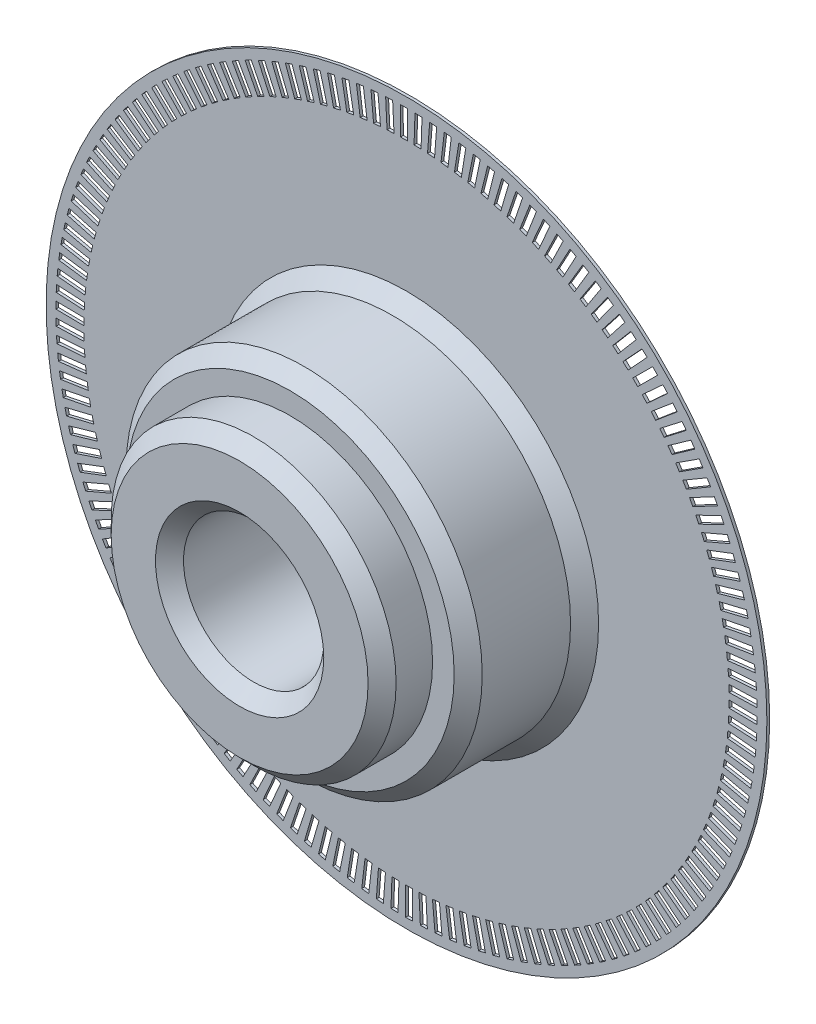
SolidWorks part; units mm, degrees
ref_plane "Płaszczyzna przednia" through (0, 0, 0) normal (0, 0, 1) x (1, 0, 0)
ref_plane "Płaszczyzna górna" through (0, 0, 0) normal (0, 1, 0) x (1, 0, 0)
ref_plane "Płaszczyzna prawa" through (0, 0, 0) normal (1, 0, 0) x (0, 0, -1)
sketch "Szkic1" plane through (0, 0, 0) normal (0, 0, 1) x (1, 0, 0)
  circle A0 centre (0, 0) radius 12.85
  dimension "D1" = 25.7
extrude "Dodanie-wyciągnięcie1" add sketch "Szkic1" along normal blind 0.1 contours A0
sketch "Szkic2" plane through (0, 0, 0.1) normal (0, 0, 1) x (1, 0, 0)
  circle A0 centre (0, 0) radius 6.35
  dimension "D1" = 12.7
extrude "Dodanie-wyciągnięcie2" add sketch "Szkic2" along normal blind 4.15
sketch "Szkic3" plane through (0, 0, 4.25) normal (0, 0, 1) x (1, 0, 0)
  circle A0 centre (0, 0) radius 5.08
  dimension "D1" = 10.16
extrude "Dodanie-wyciągnięcie3" add sketch "Szkic3" along normal blind 1.8
sketch "Szkic5" plane through (0, 0, 0) normal (0, 0, -1) x (-1, 0, 0)
  circle A0 centre (0, 0) radius 2.5
  dimension "D1" = 5
extrude "Wytnij-wyciągnięcie1" cut sketch "Szkic5" against normal through all both and the other way through all
chamfer "Sfazowanie1" distance 0.5 angle 45 5 edges at (5.08, 0, 6.05) (2.5, 0, 0) (-2.5, 0, 6.05) (6.35, 0, 0.1) (6.35, 0, 4.25)
sketch "Szkic7" plane through (0, 0, 0) normal (0, 0, -1) x (-1, 0, 0)
  line L0 (-4.4312, -10.6143) -> (-4.8067, -11.5411)
  line L3 (-3.7474, -10.8746) -> (-4.0838, -11.8163)
  line L4 (-3.7474, -10.8746) -> (-3.9829, -10.7905)
  line L5 (-4.0838, -11.8163) -> (-4.3192, -11.7322)
  line L6 (-3.9829, -10.7905) -> (-4.3192, -11.7322)
  line L7 (-3.7474, -10.8746) -> (-4.3192, -11.7322) construction
  line L8 (-4.0838, -11.8163) -> (-3.9829, -10.7905) construction
  line L9 (-4.1995, -10.7081) -> (-4.575, -11.635)
  line L10 (-4.1995, -10.7081) -> (-4.4312, -10.6143)
  line L11 (-4.575, -11.635) -> (-4.8067, -11.5411)
  line L12 (-4.8718, -10.4194) -> (-5.2858, -11.3297)
  line L13 (-4.6443, -10.5229) -> (-5.0582, -11.4332)
  line L14 (-4.6443, -10.5229) -> (-4.8718, -10.4194)
  line L15 (-5.0582, -11.4332) -> (-5.2858, -11.3297)
  line L16 (-5.3039, -10.2062) -> (-5.7556, -11.0984)
  line L17 (-5.0808, -10.3192) -> (-5.5326, -11.2113)
  line L18 (-5.0808, -10.3192) -> (-5.3039, -10.2062)
  line L19 (-5.5326, -11.2113) -> (-5.7556, -11.0984)
  line L20 (-5.7266, -9.9752) -> (-6.2153, -10.8476)
  line L21 (-5.5085, -10.0973) -> (-5.9972, -10.9698)
  line L22 (-5.5085, -10.0973) -> (-5.7266, -9.9752)
  line L23 (-5.9972, -10.9698) -> (-6.2153, -10.8476)
  line L24 (-6.1393, -9.7266) -> (-6.6641, -10.5779)
  line L25 (-5.9265, -9.8578) -> (-6.4513, -10.709)
  line L26 (-5.9265, -9.8578) -> (-6.1393, -9.7266)
  line L27 (-6.4513, -10.709) -> (-6.6641, -10.5779)
  line L28 (-6.5412, -9.461) -> (-7.1012, -10.2895)
  line L29 (-6.3341, -9.601) -> (-6.8941, -10.4295)
  line L30 (-6.3341, -9.601) -> (-6.5412, -9.461)
  line L31 (-6.8941, -10.4295) -> (-7.1012, -10.2895)
  line L32 (-6.9317, -9.1788) -> (-7.5259, -9.9831)
  line L33 (-6.7306, -9.3273) -> (-7.3248, -10.1317)
  line L34 (-6.7306, -9.3273) -> (-6.9317, -9.1788)
  line L35 (-7.3248, -10.1317) -> (-7.5259, -9.9831)
  line L36 (-7.31, -8.8805) -> (-7.9373, -9.6592)
  line L37 (-7.1153, -9.0373) -> (-7.7426, -9.816)
  line L38 (-7.1153, -9.0373) -> (-7.31, -8.8805)
  line L39 (-7.7426, -9.816) -> (-7.9373, -9.6592)
  line L40 (-7.6754, -8.5666) -> (-8.3348, -9.3184)
  line L41 (-7.4875, -8.7314) -> (-8.1469, -9.4832)
  line L42 (-7.4875, -8.7314) -> (-7.6754, -8.5666)
  line L43 (-8.1469, -9.4832) -> (-8.3348, -9.3184)
  line L44 (-8.0274, -8.2376) -> (-8.7177, -8.9612)
  line L45 (-7.8466, -8.4102) -> (-8.5369, -9.1337)
  line L46 (-7.8466, -8.4102) -> (-8.0274, -8.2376)
  line L47 (-8.5369, -9.1337) -> (-8.7177, -8.9612)
  line L48 (-8.3654, -7.8942) -> (-9.0853, -8.5882)
  line L49 (-8.1919, -8.0742) -> (-8.9118, -8.7682)
  line L50 (-8.1919, -8.0742) -> (-8.3654, -7.8942)
  line L51 (-8.9118, -8.7682) -> (-9.0853, -8.5882)
  line L52 (-8.6886, -7.537) -> (-9.437, -8.2002)
  line L53 (-8.5228, -7.7241) -> (-9.2712, -8.3874)
  line L54 (-8.5228, -7.7241) -> (-8.6886, -7.537)
  line L55 (-9.2712, -8.3874) -> (-9.437, -8.2002)
  line L56 (-8.9966, -7.1666) -> (-9.7721, -7.7979)
  line L57 (-8.8388, -7.3605) -> (-9.6143, -7.9918)
  line L58 (-8.8388, -7.3605) -> (-8.9966, -7.1666)
  line L59 (-9.6143, -7.9918) -> (-9.7721, -7.7979)
  line L60 (-9.2888, -6.7835) -> (-10.0901, -7.3818)
  line L61 (-9.1392, -6.9839) -> (-9.9405, -7.5821)
  line L62 (-9.1392, -6.9839) -> (-9.2888, -6.7835)
  line L63 (-9.9405, -7.5821) -> (-10.0901, -7.3818)
  line L64 (-9.5647, -6.3886) -> (-10.3904, -6.9528)
  line L65 (-9.4237, -6.595) -> (-10.2493, -7.1592)
  line L66 (-9.4237, -6.595) -> (-9.5647, -6.3886)
  line L67 (-10.2493, -7.1592) -> (-10.3904, -6.9528)
  line L68 (-9.8239, -5.9825) -> (-10.6724, -6.5116)
  line L69 (-9.6916, -6.1946) -> (-10.5401, -6.7237)
  line L70 (-9.6916, -6.1946) -> (-9.8239, -5.9825)
  line L71 (-10.5401, -6.7237) -> (-10.6724, -6.5116)
  line L72 (-10.0658, -5.5659) -> (-10.9357, -6.059)
  line L73 (-9.9425, -5.7833) -> (-10.8124, -6.2765)
  line L74 (-9.9425, -5.7833) -> (-10.0658, -5.5659)
  line L75 (-10.8124, -6.2765) -> (-10.9357, -6.059)
  line L76 (-10.29, -5.1395) -> (-11.1798, -5.5957)
  line L77 (-10.1759, -5.3619) -> (-11.0658, -5.8182)
  line L78 (-10.1759, -5.3619) -> (-10.29, -5.1395)
  line L79 (-11.0658, -5.8182) -> (-11.1798, -5.5957)
  line L80 (-10.4962, -4.7041) -> (-11.4044, -5.1227)
  line L81 (-10.3915, -4.9311) -> (-11.2997, -5.3497)
  line L82 (-10.3915, -4.9311) -> (-10.4962, -4.7041)
  line L83 (-11.2997, -5.3497) -> (-11.4044, -5.1227)
  line L84 (-10.684, -4.2604) -> (-11.6089, -4.6406)
  line L85 (-10.5889, -4.4916) -> (-11.5138, -4.8718)
  line L86 (-10.5889, -4.4916) -> (-10.684, -4.2604)
  line L87 (-11.5138, -4.8718) -> (-11.6089, -4.6406)
  line L88 (-10.853, -3.8093) -> (-11.793, -4.1504)
  line L89 (-10.7677, -4.0443) -> (-11.7077, -4.3854)
  line L90 (-10.7677, -4.0443) -> (-10.853, -3.8093)
  line L91 (-11.7077, -4.3854) -> (-11.793, -4.1504)
  line L92 (-11.003, -3.3514) -> (-11.9565, -3.6529)
  line L93 (-10.9276, -3.5898) -> (-11.8811, -3.8913)
  line L94 (-10.9276, -3.5898) -> (-11.003, -3.3514)
  line L95 (-11.8811, -3.8913) -> (-11.9565, -3.6529)
  line L96 (-11.1337, -2.8877) -> (-12.099, -3.149)
  line L97 (-11.0684, -3.1291) -> (-12.0336, -3.3903)
  line L98 (-11.0684, -3.1291) -> (-11.1337, -2.8877)
  line L99 (-12.0336, -3.3903) -> (-12.099, -3.149)
  line L100 (-11.2449, -2.419) -> (-12.2202, -2.6396)
  line L101 (-11.1897, -2.6628) -> (-12.1651, -2.8835)
  line L102 (-11.1897, -2.6628) -> (-11.2449, -2.419)
  line L103 (-12.1651, -2.8835) -> (-12.2202, -2.6396)
  line L104 (-11.3363, -1.946) -> (-12.32, -2.1256)
  line L105 (-11.2914, -2.1919) -> (-12.2751, -2.3715)
  line L106 (-11.2914, -2.1919) -> (-11.3363, -1.946)
  line L107 (-12.2751, -2.3715) -> (-12.32, -2.1256)
  line L108 (-11.4078, -1.4696) -> (-12.3982, -1.6078)
  line L109 (-11.3733, -1.7172) -> (-12.3637, -1.8554)
  line L110 (-11.3733, -1.7172) -> (-11.4078, -1.4696)
  line L111 (-12.3637, -1.8554) -> (-12.3982, -1.6078)
  line L112 (-11.4594, -0.9906) -> (-12.4547, -1.0872)
  line L113 (-11.4352, -1.2394) -> (-12.4305, -1.336)
  line L114 (-11.4352, -1.2394) -> (-11.4594, -0.9906)
  line L115 (-12.4305, -1.336) -> (-12.4547, -1.0872)
  line L116 (-11.4908, -0.5098) -> (-12.4893, -0.5647)
  line L117 (-11.4771, -0.7594) -> (-12.4756, -0.8143)
  line L118 (-11.4771, -0.7594) -> (-11.4908, -0.5098)
  line L119 (-12.4756, -0.8143) -> (-12.4893, -0.5647)
  line L120 (-11.5021, -0.0282) -> (-12.502, -0.0412)
  line L121 (-11.4988, -0.2782) -> (-12.4987, -0.2912)
  line L122 (-11.4988, -0.2782) -> (-11.5021, -0.0282)
  line L123 (-12.4987, -0.2912) -> (-12.502, -0.0412)
  line L124 (-11.4932, 0.4535) -> (-12.4927, 0.4824)
  line L125 (-11.5004, 0.2036) -> (-12.5, 0.2325)
  line L126 (-11.5004, 0.2036) -> (-11.4932, 0.4535)
  line L127 (-12.5, 0.2325) -> (-12.4927, 0.4824)
  line L128 (-11.4641, 0.9344) -> (-12.4616, 1.0051)
  line L129 (-11.4818, 0.685) -> (-12.4793, 0.7557)
  line L130 (-11.4818, 0.685) -> (-11.4641, 0.9344)
  line L131 (-12.4793, 0.7557) -> (-12.4616, 1.0051)
  line L132 (-11.4149, 1.4136) -> (-12.4086, 1.526)
  line L133 (-11.443, 1.1652) -> (-12.4367, 1.2776)
  line L134 (-11.443, 1.1652) -> (-11.4149, 1.4136)
  line L135 (-12.4367, 1.2776) -> (-12.4086, 1.526)
  line L136 (-11.3457, 1.8904) -> (-12.3338, 2.0443)
  line L137 (-11.3842, 1.6434) -> (-12.3723, 1.7973)
  line L138 (-11.3842, 1.6434) -> (-11.3457, 1.8904)
  line L139 (-12.3723, 1.7973) -> (-12.3338, 2.0443)
  line L140 (-11.2566, 2.3638) -> (-12.2374, 2.559)
  line L141 (-11.3054, 2.1187) -> (-12.2861, 2.3138)
  line L142 (-11.3054, 2.1187) -> (-11.2566, 2.3638)
  line L143 (-12.2861, 2.3138) -> (-12.2374, 2.559)
  line L144 (-11.1477, 2.8331) -> (-12.1195, 3.0692)
  line L145 (-11.2067, 2.5902) -> (-12.1785, 2.8263)
  line L146 (-11.2067, 2.5902) -> (-11.1477, 2.8331)
  line L147 (-12.1785, 2.8263) -> (-12.1195, 3.0692)
  line L148 (-11.0193, 3.2975) -> (-11.9803, 3.574)
  line L149 (-11.0884, 3.0572) -> (-12.0494, 3.3338)
  line L150 (-11.0884, 3.0572) -> (-11.0193, 3.2975)
  line L151 (-12.0494, 3.3338) -> (-11.9803, 3.574)
  line L152 (-10.8715, 3.756) -> (-11.8201, 4.0726)
  line L153 (-10.9507, 3.5189) -> (-11.8993, 3.8354)
  line L154 (-10.9507, 3.5189) -> (-10.8715, 3.756)
  line L155 (-11.8993, 3.8354) -> (-11.8201, 4.0726)
  line L156 (-10.7047, 4.208) -> (-11.6392, 4.564)
  line L157 (-10.7937, 3.9744) -> (-11.7282, 4.3303)
  line L158 (-10.7937, 3.9744) -> (-10.7047, 4.208)
  line L159 (-11.7282, 4.3303) -> (-11.6392, 4.564)
  line L160 (-10.5191, 4.6526) -> (-11.4379, 5.0474)
  line L161 (-10.6178, 4.4229) -> (-11.5366, 4.8177)
  line L162 (-10.6178, 4.4229) -> (-10.5191, 4.6526)
  line L163 (-11.5366, 4.8177) -> (-11.4379, 5.0474)
  line L164 (-10.3151, 5.089) -> (-11.2165, 5.5219)
  line L165 (-10.4233, 4.8636) -> (-11.3247, 5.2965)
  line L166 (-10.4233, 4.8636) -> (-10.3151, 5.089)
  line L167 (-11.3247, 5.2965) -> (-11.2165, 5.5219)
  line L168 (-10.0929, 5.5165) -> (-10.9754, 5.9868)
  line L169 (-10.2105, 5.2958) -> (-11.093, 5.7661)
  line L170 (-10.2105, 5.2958) -> (-10.0929, 5.5165)
  line L171 (-11.093, 5.7661) -> (-10.9754, 5.9868)
  line L172 (-9.8531, 5.9343) -> (-10.7151, 6.4411)
  line L173 (-9.9798, 5.7188) -> (-10.8418, 6.2256)
  line L174 (-9.9798, 5.7188) -> (-9.8531, 5.9343)
  line L175 (-10.8418, 6.2256) -> (-10.7151, 6.4411)
  line L176 (-9.5959, 6.3417) -> (-10.436, 6.8842)
  line L177 (-9.7315, 6.1317) -> (-10.5716, 6.6741)
  line L178 (-9.7315, 6.1317) -> (-9.5959, 6.3417)
  line L179 (-10.5716, 6.6741) -> (-10.436, 6.8842)
  line L180 (-9.3219, 6.7379) -> (-10.1385, 7.3151)
  line L181 (-9.4662, 6.5338) -> (-10.2828, 7.111)
  line L182 (-9.4662, 6.5338) -> (-9.3219, 6.7379)
  line L183 (-10.2828, 7.111) -> (-10.1385, 7.3151)
  line L184 (-9.0316, 7.1224) -> (-9.8233, 7.7333)
  line L185 (-9.1843, 6.9245) -> (-9.976, 7.5354)
  line L186 (-9.1843, 6.9245) -> (-9.0316, 7.1224)
  line L187 (-9.976, 7.5354) -> (-9.8233, 7.7333)
  line L188 (-8.7254, 7.4944) -> (-9.4909, 8.1379)
  line L189 (-8.8863, 7.303) -> (-9.6517, 7.9465)
  line L190 (-8.8863, 7.303) -> (-8.7254, 7.4944)
  line L191 (-9.6517, 7.9465) -> (-9.4909, 8.1379)
  line L192 (-8.4039, 7.8532) -> (-9.1418, 8.5282)
  line L193 (-8.5727, 7.6687) -> (-9.3105, 8.3437)
  line L194 (-8.5727, 7.6687) -> (-8.4039, 7.8532)
  line L195 (-9.3105, 8.3437) -> (-9.1418, 8.5282)
  line L196 (-8.0677, 8.1982) -> (-8.7766, 8.9035)
  line L197 (-8.244, 8.021) -> (-8.9529, 8.7263)
  line L198 (-8.244, 8.021) -> (-8.0677, 8.1982)
  line L199 (-8.9529, 8.7263) -> (-8.7766, 8.9035)
  line L200 (-7.7173, 8.5288) -> (-8.3961, 9.2632)
  line L201 (-7.9009, 8.3592) -> (-8.5797, 9.0935)
  line L202 (-7.9009, 8.3592) -> (-7.7173, 8.5288)
  line L203 (-8.5797, 9.0935) -> (-8.3961, 9.2632)
  line L204 (-7.3534, 8.8445) -> (-8.0008, 9.6067)
  line L205 (-7.5439, 8.6827) -> (-8.1914, 9.4448)
  line L206 (-7.5439, 8.6827) -> (-7.3534, 8.8445)
  line L207 (-8.1914, 9.4448) -> (-8.0008, 9.6067)
  line L208 (-6.9766, 9.1447) -> (-7.5915, 9.9333)
  line L209 (-7.1737, 8.991) -> (-7.7887, 9.7796)
  line L210 (-7.1737, 8.991) -> (-6.9766, 9.1447)
  line L211 (-7.7887, 9.7796) -> (-7.5915, 9.9333)
  line L212 (-6.5875, 9.4288) -> (-7.1689, 10.2425)
  line L213 (-6.7909, 9.2835) -> (-7.3723, 10.0971)
  line L214 (-6.7909, 9.2835) -> (-6.5875, 9.4288)
  line L215 (-7.3723, 10.0971) -> (-7.1689, 10.2425)
  line L216 (-6.1869, 9.6964) -> (-6.7337, 10.5337)
  line L217 (-6.3962, 9.5597) -> (-6.943, 10.397)
  line L218 (-6.3962, 9.5597) -> (-6.1869, 9.6964)
  line L219 (-6.943, 10.397) -> (-6.7337, 10.5337)
  line L220 (-5.7754, 9.947) -> (-6.2867, 10.8064)
  line L221 (-5.9903, 9.8192) -> (-6.5015, 10.6786)
  line L222 (-5.9903, 9.8192) -> (-5.7754, 9.947)
  line L223 (-6.5015, 10.6786) -> (-6.2867, 10.8064)
  line L224 (-5.3538, 10.1801) -> (-5.8286, 11.0602)
  line L225 (-5.5739, 10.0614) -> (-6.0487, 10.9415)
  line L226 (-5.5739, 10.0614) -> (-5.3538, 10.1801)
  line L227 (-6.0487, 10.9415) -> (-5.8286, 11.0602)
  line L228 (-4.9228, 10.3954) -> (-5.3604, 11.2946)
  line L229 (-5.1476, 10.286) -> (-5.5852, 11.1852)
  line L230 (-5.1476, 10.286) -> (-4.9228, 10.3954)
  line L231 (-5.5852, 11.1852) -> (-5.3604, 11.2946)
  line L232 (-4.4832, 10.5924) -> (-4.8827, 11.5091)
  line L233 (-4.7124, 10.4925) -> (-5.1119, 11.4093)
  line L234 (-4.7124, 10.4925) -> (-4.4832, 10.5924)
  line L235 (-5.1119, 11.4093) -> (-4.8827, 11.5091)
  line L236 (-4.0357, 10.7709) -> (-4.3965, 11.7035)
  line L237 (-4.2689, 10.6807) -> (-4.6296, 11.6133)
  line L238 (-4.2689, 10.6807) -> (-4.0357, 10.7709)
  line L239 (-4.6296, 11.6133) -> (-4.3965, 11.7035)
  line L240 (-3.5811, 10.9304) -> (-3.9025, 11.8774)
  line L241 (-3.8179, 10.8501) -> (-4.1393, 11.797)
  line L242 (-3.8179, 10.8501) -> (-3.5811, 10.9304)
  line L243 (-4.1393, 11.797) -> (-3.9025, 11.8774)
  line L244 (-3.1203, 11.0708) -> (-3.4017, 12.0304)
  line L245 (-3.3602, 11.0004) -> (-3.6416, 11.96)
  line L246 (-3.3602, 11.0004) -> (-3.1203, 11.0708)
  line L247 (-3.6416, 11.96) -> (-3.4017, 12.0304)
  line L248 (-2.6539, 11.1917) -> (-2.895, 12.1623)
  line L249 (-2.8966, 11.1315) -> (-3.1376, 12.102)
  line L250 (-2.8966, 11.1315) -> (-2.6539, 11.1917)
  line L251 (-3.1376, 12.102) -> (-2.895, 12.1623)
  line L252 (-2.183, 11.2931) -> (-2.3831, 12.2728)
  line L253 (-2.4279, 11.243) -> (-2.6281, 12.2228)
  line L254 (-2.4279, 11.243) -> (-2.183, 11.2931)
  line L255 (-2.6281, 12.2228) -> (-2.3831, 12.2728)
  line L256 (-1.7081, 11.3746) -> (-1.8671, 12.3618)
  line L257 (-1.955, 11.3348) -> (-2.1139, 12.3221)
  line L258 (-1.955, 11.3348) -> (-1.7081, 11.3746)
  line L259 (-2.1139, 12.3221) -> (-1.8671, 12.3618)
  line L260 (-1.2303, 11.4361) -> (-1.3478, 12.4292)
  line L261 (-1.4786, 11.4067) -> (-1.5961, 12.3998)
  line L262 (-1.4786, 11.4067) -> (-1.2303, 11.4361)
  line L263 (-1.5961, 12.3998) -> (-1.3478, 12.4292)
  line L264 (-0.7503, 11.4776) -> (-0.8261, 12.4747)
  line L265 (-0.9996, 11.4587) -> (-1.0754, 12.4558)
  line L266 (-0.9996, 11.4587) -> (-0.7503, 11.4776)
  line L267 (-1.0754, 12.4558) -> (-0.8261, 12.4747)
  line L268 (-0.2691, 11.499) -> (-0.303, 12.4984)
  line L269 (-0.5189, 11.4905) -> (-0.5529, 12.4899)
  line L270 (-0.5189, 11.4905) -> (-0.2691, 11.499)
  line L271 (-0.5529, 12.4899) -> (-0.303, 12.4984)
  line L272 (0.2127, 11.5001) -> (0.2206, 12.5001)
  line L273 (-0.0373, 11.5021) -> (-0.0294, 12.5021)
  line L274 (-0.0373, 11.5021) -> (0.2127, 11.5001)
  line L275 (-0.0294, 12.5021) -> (0.2206, 12.5001)
  line L276 (0.6941, 11.4811) -> (0.7439, 12.4799)
  line L277 (0.4444, 11.4936) -> (0.4942, 12.4923)
  line L278 (0.4444, 11.4936) -> (0.6941, 11.4811)
  line L279 (0.4942, 12.4923) -> (0.7439, 12.4799)
  line L280 (1.1743, 11.442) -> (1.2658, 12.4378)
  line L281 (0.9253, 11.4649) -> (1.0169, 12.4607)
  line L282 (0.9253, 11.4649) -> (1.1743, 11.442)
  line L283 (1.0169, 12.4607) -> (1.2658, 12.4378)
  line L284 (1.6524, 11.3828) -> (1.7856, 12.3739)
  line L285 (1.4046, 11.4161) -> (1.5378, 12.4072)
  line L286 (1.4046, 11.4161) -> (1.6524, 11.3828)
  line L287 (1.5378, 12.4072) -> (1.7856, 12.3739)
  line L288 (2.1276, 11.3036) -> (2.3022, 12.2883)
  line L289 (1.8814, 11.3473) -> (2.056, 12.3319)
  line L290 (1.8814, 11.3473) -> (2.1276, 11.3036)
  line L291 (2.056, 12.3319) -> (2.3022, 12.2883)
  line L292 (2.5991, 11.2046) -> (2.8147, 12.1811)
  line L293 (2.355, 11.2585) -> (2.5706, 12.235)
  line L294 (2.355, 11.2585) -> (2.5991, 11.2046)
  line L295 (2.5706, 12.235) -> (2.8147, 12.1811)
  line L296 (3.066, 11.0859) -> (3.3223, 12.0525)
  line L297 (2.8243, 11.15) -> (3.0807, 12.1166)
  line L298 (2.8243, 11.15) -> (3.066, 11.0859)
  line L299 (3.0807, 12.1166) -> (3.3223, 12.0525)
  line L300 (3.5275, 10.9478) -> (3.8241, 11.9028)
  line L301 (3.2888, 11.022) -> (3.5854, 11.977)
  line L302 (3.2888, 11.022) -> (3.5275, 10.9478)
  line L303 (3.5854, 11.977) -> (3.8241, 11.9028)
  line L304 (3.9829, 10.7905) -> (4.3192, 11.7322)
  line L305 (3.7474, 10.8746) -> (4.0838, 11.8163)
  line L306 (3.7474, 10.8746) -> (3.9829, 10.7905)
  line L307 (4.0838, 11.8163) -> (4.3192, 11.7322)
  line L308 (4.4312, 10.6143) -> (4.8067, 11.5411)
  line L309 (4.1995, 10.7081) -> (4.575, 11.635)
  line L310 (4.1995, 10.7081) -> (4.4312, 10.6143)
  line L311 (4.575, 11.635) -> (4.8067, 11.5411)
  line L312 (4.8718, 10.4194) -> (5.2858, 11.3297)
  line L313 (4.6443, 10.5229) -> (5.0582, 11.4332)
  line L314 (4.6443, 10.5229) -> (4.8718, 10.4194)
  line L315 (5.0582, 11.4332) -> (5.2858, 11.3297)
  line L316 (5.3039, 10.2062) -> (5.7556, 11.0984)
  line L317 (5.0808, 10.3192) -> (5.5326, 11.2113)
  line L318 (5.0808, 10.3192) -> (5.3039, 10.2062)
  line L319 (5.5326, 11.2113) -> (5.7556, 11.0984)
  line L320 (5.7266, 9.9752) -> (6.2153, 10.8476)
  line L321 (5.5085, 10.0973) -> (5.9972, 10.9698)
  line L322 (5.5085, 10.0973) -> (5.7266, 9.9752)
  line L323 (5.9972, 10.9698) -> (6.2153, 10.8476)
  line L324 (6.1393, 9.7266) -> (6.6641, 10.5779)
  line L325 (5.9265, 9.8578) -> (6.4513, 10.709)
  line L326 (5.9265, 9.8578) -> (6.1393, 9.7266)
  line L327 (6.4513, 10.709) -> (6.6641, 10.5779)
  line L328 (6.5412, 9.461) -> (7.1012, 10.2895)
  line L329 (6.3341, 9.601) -> (6.8941, 10.4295)
  line L330 (6.3341, 9.601) -> (6.5412, 9.461)
  line L331 (6.8941, 10.4295) -> (7.1012, 10.2895)
  line L332 (6.9317, 9.1788) -> (7.5259, 9.9831)
  line L333 (6.7306, 9.3273) -> (7.3248, 10.1317)
  line L334 (6.7306, 9.3273) -> (6.9317, 9.1788)
  line L335 (7.3248, 10.1317) -> (7.5259, 9.9831)
  line L336 (7.31, 8.8805) -> (7.9373, 9.6592)
  line L337 (7.1153, 9.0373) -> (7.7426, 9.816)
  line L338 (7.1153, 9.0373) -> (7.31, 8.8805)
  line L339 (7.7426, 9.816) -> (7.9373, 9.6592)
  line L340 (7.6754, 8.5666) -> (8.3348, 9.3184)
  line L341 (7.4875, 8.7314) -> (8.1469, 9.4832)
  line L342 (7.4875, 8.7314) -> (7.6754, 8.5666)
  line L343 (8.1469, 9.4832) -> (8.3348, 9.3184)
  line L344 (8.0274, 8.2376) -> (8.7177, 8.9612)
  line L345 (7.8466, 8.4102) -> (8.5369, 9.1337)
  line L346 (7.8466, 8.4102) -> (8.0274, 8.2376)
  line L347 (8.5369, 9.1337) -> (8.7177, 8.9612)
  line L348 (8.3654, 7.8942) -> (9.0853, 8.5882)
  line L349 (8.1919, 8.0742) -> (8.9118, 8.7682)
  line L350 (8.1919, 8.0742) -> (8.3654, 7.8942)
  line L351 (8.9118, 8.7682) -> (9.0853, 8.5882)
  line L352 (8.6886, 7.537) -> (9.437, 8.2002)
  line L353 (8.5228, 7.7241) -> (9.2712, 8.3874)
  line L354 (8.5228, 7.7241) -> (8.6886, 7.537)
  line L355 (9.2712, 8.3874) -> (9.437, 8.2002)
  line L356 (8.9966, 7.1666) -> (9.7721, 7.7979)
  line L357 (8.8388, 7.3605) -> (9.6143, 7.9918)
  line L358 (8.8388, 7.3605) -> (8.9966, 7.1666)
  line L359 (9.6143, 7.9918) -> (9.7721, 7.7979)
  line L360 (9.2888, 6.7835) -> (10.0901, 7.3818)
  line L361 (9.1392, 6.9839) -> (9.9405, 7.5821)
  line L362 (9.1392, 6.9839) -> (9.2888, 6.7835)
  line L363 (9.9405, 7.5821) -> (10.0901, 7.3818)
  line L364 (9.5647, 6.3886) -> (10.3904, 6.9528)
  line L365 (9.4237, 6.595) -> (10.2493, 7.1592)
  line L366 (9.4237, 6.595) -> (9.5647, 6.3886)
  line L367 (10.2493, 7.1592) -> (10.3904, 6.9528)
  line L368 (9.8239, 5.9825) -> (10.6724, 6.5116)
  line L369 (9.6916, 6.1946) -> (10.5401, 6.7237)
  line L370 (9.6916, 6.1946) -> (9.8239, 5.9825)
  line L371 (10.5401, 6.7237) -> (10.6724, 6.5116)
  line L372 (10.0658, 5.5659) -> (10.9357, 6.059)
  line L373 (9.9425, 5.7833) -> (10.8124, 6.2765)
  line L374 (9.9425, 5.7833) -> (10.0658, 5.5659)
  line L375 (10.8124, 6.2765) -> (10.9357, 6.059)
  line L376 (10.29, 5.1395) -> (11.1798, 5.5957)
  line L377 (10.1759, 5.3619) -> (11.0658, 5.8182)
  line L378 (10.1759, 5.3619) -> (10.29, 5.1395)
  line L379 (11.0658, 5.8182) -> (11.1798, 5.5957)
  line L380 (10.4962, 4.7041) -> (11.4044, 5.1227)
  line L381 (10.3915, 4.9311) -> (11.2997, 5.3497)
  line L382 (10.3915, 4.9311) -> (10.4962, 4.7041)
  line L383 (11.2997, 5.3497) -> (11.4044, 5.1227)
  line L384 (10.684, 4.2604) -> (11.6089, 4.6406)
  line L385 (10.5889, 4.4916) -> (11.5138, 4.8718)
  line L386 (10.5889, 4.4916) -> (10.684, 4.2604)
  line L387 (11.5138, 4.8718) -> (11.6089, 4.6406)
  line L388 (10.853, 3.8093) -> (11.793, 4.1504)
  line L389 (10.7677, 4.0443) -> (11.7077, 4.3854)
  line L390 (10.7677, 4.0443) -> (10.853, 3.8093)
  line L391 (11.7077, 4.3854) -> (11.793, 4.1504)
  line L392 (11.003, 3.3514) -> (11.9565, 3.6529)
  line L393 (10.9276, 3.5898) -> (11.8811, 3.8913)
  line L394 (10.9276, 3.5898) -> (11.003, 3.3514)
  line L395 (11.8811, 3.8913) -> (11.9565, 3.6529)
  line L396 (11.1337, 2.8877) -> (12.099, 3.149)
  line L397 (11.0684, 3.1291) -> (12.0336, 3.3903)
  line L398 (11.0684, 3.1291) -> (11.1337, 2.8877)
  line L399 (12.0336, 3.3903) -> (12.099, 3.149)
  line L400 (11.2449, 2.419) -> (12.2202, 2.6396)
  line L401 (11.1897, 2.6628) -> (12.1651, 2.8835)
  line L402 (11.1897, 2.6628) -> (11.2449, 2.419)
  line L403 (12.1651, 2.8835) -> (12.2202, 2.6396)
  line L404 (11.3363, 1.946) -> (12.32, 2.1256)
  line L405 (11.2914, 2.1919) -> (12.2751, 2.3715)
  line L406 (11.2914, 2.1919) -> (11.3363, 1.946)
  line L407 (12.2751, 2.3715) -> (12.32, 2.1256)
  line L408 (11.4078, 1.4696) -> (12.3982, 1.6078)
  line L409 (11.3733, 1.7172) -> (12.3637, 1.8554)
  line L410 (11.3733, 1.7172) -> (11.4078, 1.4696)
  line L411 (12.3637, 1.8554) -> (12.3982, 1.6078)
  line L412 (11.4594, 0.9906) -> (12.4547, 1.0872)
  line L413 (11.4352, 1.2394) -> (12.4305, 1.336)
  line L414 (11.4352, 1.2394) -> (11.4594, 0.9906)
  line L415 (12.4305, 1.336) -> (12.4547, 1.0872)
  line L416 (11.4908, 0.5098) -> (12.4893, 0.5647)
  line L417 (11.4771, 0.7594) -> (12.4756, 0.8143)
  line L418 (11.4771, 0.7594) -> (11.4908, 0.5098)
  line L419 (12.4756, 0.8143) -> (12.4893, 0.5647)
  line L420 (11.5021, 0.0282) -> (12.502, 0.0412)
  line L421 (11.4988, 0.2782) -> (12.4987, 0.2912)
  line L422 (11.4988, 0.2782) -> (11.5021, 0.0282)
  line L423 (12.4987, 0.2912) -> (12.502, 0.0412)
  line L424 (11.4932, -0.4535) -> (12.4927, -0.4824)
  line L425 (11.5004, -0.2036) -> (12.5, -0.2325)
  line L426 (11.5004, -0.2036) -> (11.4932, -0.4535)
  line L427 (12.5, -0.2325) -> (12.4927, -0.4824)
  line L428 (11.4641, -0.9344) -> (12.4616, -1.0051)
  line L429 (11.4818, -0.685) -> (12.4793, -0.7557)
  line L430 (11.4818, -0.685) -> (11.4641, -0.9344)
  line L431 (12.4793, -0.7557) -> (12.4616, -1.0051)
  line L432 (11.4149, -1.4136) -> (12.4086, -1.526)
  line L433 (11.443, -1.1652) -> (12.4367, -1.2776)
  line L434 (11.443, -1.1652) -> (11.4149, -1.4136)
  line L435 (12.4367, -1.2776) -> (12.4086, -1.526)
  line L436 (11.3457, -1.8904) -> (12.3338, -2.0443)
  line L437 (11.3842, -1.6434) -> (12.3723, -1.7973)
  line L438 (11.3842, -1.6434) -> (11.3457, -1.8904)
  line L439 (12.3723, -1.7973) -> (12.3338, -2.0443)
  line L440 (11.2566, -2.3638) -> (12.2374, -2.559)
  line L441 (11.3054, -2.1187) -> (12.2861, -2.3138)
  line L442 (11.3054, -2.1187) -> (11.2566, -2.3638)
  line L443 (12.2861, -2.3138) -> (12.2374, -2.559)
  line L444 (11.1477, -2.8331) -> (12.1195, -3.0692)
  line L445 (11.2067, -2.5902) -> (12.1785, -2.8263)
  line L446 (11.2067, -2.5902) -> (11.1477, -2.8331)
  line L447 (12.1785, -2.8263) -> (12.1195, -3.0692)
  line L448 (11.0193, -3.2975) -> (11.9803, -3.574)
  line L449 (11.0884, -3.0572) -> (12.0494, -3.3338)
  line L450 (11.0884, -3.0572) -> (11.0193, -3.2975)
  line L451 (12.0494, -3.3338) -> (11.9803, -3.574)
  line L452 (10.8715, -3.756) -> (11.8201, -4.0726)
  line L453 (10.9507, -3.5189) -> (11.8993, -3.8354)
  line L454 (10.9507, -3.5189) -> (10.8715, -3.756)
  line L455 (11.8993, -3.8354) -> (11.8201, -4.0726)
  line L456 (10.7047, -4.208) -> (11.6392, -4.564)
  line L457 (10.7937, -3.9744) -> (11.7282, -4.3303)
  line L458 (10.7937, -3.9744) -> (10.7047, -4.208)
  line L459 (11.7282, -4.3303) -> (11.6392, -4.564)
  line L460 (10.5191, -4.6526) -> (11.4379, -5.0474)
  line L461 (10.6178, -4.4229) -> (11.5366, -4.8177)
  line L462 (10.6178, -4.4229) -> (10.5191, -4.6526)
  line L463 (11.5366, -4.8177) -> (11.4379, -5.0474)
  line L464 (10.3151, -5.089) -> (11.2165, -5.5219)
  line L465 (10.4233, -4.8636) -> (11.3247, -5.2965)
  line L466 (10.4233, -4.8636) -> (10.3151, -5.089)
  line L467 (11.3247, -5.2965) -> (11.2165, -5.5219)
  line L468 (10.0929, -5.5165) -> (10.9754, -5.9868)
  line L469 (10.2105, -5.2958) -> (11.093, -5.7661)
  line L470 (10.2105, -5.2958) -> (10.0929, -5.5165)
  line L471 (11.093, -5.7661) -> (10.9754, -5.9868)
  line L472 (9.8531, -5.9343) -> (10.7151, -6.4411)
  line L473 (9.9798, -5.7188) -> (10.8418, -6.2256)
  line L474 (9.9798, -5.7188) -> (9.8531, -5.9343)
  line L475 (10.8418, -6.2256) -> (10.7151, -6.4411)
  line L476 (9.5959, -6.3417) -> (10.436, -6.8842)
  line L477 (9.7315, -6.1317) -> (10.5716, -6.6741)
  line L478 (9.7315, -6.1317) -> (9.5959, -6.3417)
  line L479 (10.5716, -6.6741) -> (10.436, -6.8842)
  line L480 (9.3219, -6.7379) -> (10.1385, -7.3151)
  line L481 (9.4662, -6.5338) -> (10.2828, -7.111)
  line L482 (9.4662, -6.5338) -> (9.3219, -6.7379)
  line L483 (10.2828, -7.111) -> (10.1385, -7.3151)
  line L484 (9.0316, -7.1224) -> (9.8233, -7.7333)
  line L485 (9.1843, -6.9245) -> (9.976, -7.5354)
  line L486 (9.1843, -6.9245) -> (9.0316, -7.1224)
  line L487 (9.976, -7.5354) -> (9.8233, -7.7333)
  line L488 (8.7254, -7.4944) -> (9.4909, -8.1379)
  line L489 (8.8863, -7.303) -> (9.6517, -7.9465)
  line L490 (8.8863, -7.303) -> (8.7254, -7.4944)
  line L491 (9.6517, -7.9465) -> (9.4909, -8.1379)
  line L492 (8.4039, -7.8532) -> (9.1418, -8.5282)
  line L493 (8.5727, -7.6687) -> (9.3105, -8.3437)
  line L494 (8.5727, -7.6687) -> (8.4039, -7.8532)
  line L495 (9.3105, -8.3437) -> (9.1418, -8.5282)
  line L496 (8.0677, -8.1982) -> (8.7766, -8.9035)
  line L497 (8.244, -8.021) -> (8.9529, -8.7263)
  line L498 (8.244, -8.021) -> (8.0677, -8.1982)
  line L499 (8.9529, -8.7263) -> (8.7766, -8.9035)
  line L500 (7.7173, -8.5288) -> (8.3961, -9.2632)
  line L501 (7.9009, -8.3592) -> (8.5797, -9.0935)
  line L502 (7.9009, -8.3592) -> (7.7173, -8.5288)
  line L503 (8.5797, -9.0935) -> (8.3961, -9.2632)
  line L504 (7.3534, -8.8445) -> (8.0008, -9.6067)
  line L505 (7.5439, -8.6827) -> (8.1914, -9.4448)
  line L506 (7.5439, -8.6827) -> (7.3534, -8.8445)
  line L507 (8.1914, -9.4448) -> (8.0008, -9.6067)
  line L508 (6.9766, -9.1447) -> (7.5915, -9.9333)
  line L509 (7.1737, -8.991) -> (7.7887, -9.7796)
  line L510 (7.1737, -8.991) -> (6.9766, -9.1447)
  line L511 (7.7887, -9.7796) -> (7.5915, -9.9333)
  line L512 (6.5875, -9.4288) -> (7.1689, -10.2425)
  line L513 (6.7909, -9.2835) -> (7.3723, -10.0971)
  line L514 (6.7909, -9.2835) -> (6.5875, -9.4288)
  line L515 (7.3723, -10.0971) -> (7.1689, -10.2425)
  line L516 (6.1869, -9.6964) -> (6.7337, -10.5337)
  line L517 (6.3962, -9.5597) -> (6.943, -10.397)
  line L518 (6.3962, -9.5597) -> (6.1869, -9.6964)
  line L519 (6.943, -10.397) -> (6.7337, -10.5337)
  line L520 (5.7754, -9.947) -> (6.2867, -10.8064)
  line L521 (5.9903, -9.8192) -> (6.5015, -10.6786)
  line L522 (5.9903, -9.8192) -> (5.7754, -9.947)
  line L523 (6.5015, -10.6786) -> (6.2867, -10.8064)
  line L524 (5.3538, -10.1801) -> (5.8286, -11.0602)
  line L525 (5.5739, -10.0614) -> (6.0487, -10.9415)
  line L526 (5.5739, -10.0614) -> (5.3538, -10.1801)
  line L527 (6.0487, -10.9415) -> (5.8286, -11.0602)
  line L528 (4.9228, -10.3954) -> (5.3604, -11.2946)
  line L529 (5.1476, -10.286) -> (5.5852, -11.1852)
  line L530 (5.1476, -10.286) -> (4.9228, -10.3954)
  line L531 (5.5852, -11.1852) -> (5.3604, -11.2946)
  line L532 (4.4832, -10.5924) -> (4.8827, -11.5091)
  line L533 (4.7124, -10.4925) -> (5.1119, -11.4093)
  line L534 (4.7124, -10.4925) -> (4.4832, -10.5924)
  line L535 (5.1119, -11.4093) -> (4.8827, -11.5091)
  line L536 (4.0357, -10.7709) -> (4.3965, -11.7035)
  line L537 (4.2689, -10.6807) -> (4.6296, -11.6133)
  line L538 (4.2689, -10.6807) -> (4.0357, -10.7709)
  line L539 (4.6296, -11.6133) -> (4.3965, -11.7035)
  line L540 (3.5811, -10.9304) -> (3.9025, -11.8774)
  line L541 (3.8179, -10.8501) -> (4.1393, -11.797)
  line L542 (3.8179, -10.8501) -> (3.5811, -10.9304)
  line L543 (4.1393, -11.797) -> (3.9025, -11.8774)
  line L544 (3.1203, -11.0708) -> (3.4017, -12.0304)
  line L545 (3.3602, -11.0004) -> (3.6416, -11.96)
  line L546 (3.3602, -11.0004) -> (3.1203, -11.0708)
  line L547 (3.6416, -11.96) -> (3.4017, -12.0304)
  line L548 (2.6539, -11.1917) -> (2.895, -12.1623)
  line L549 (2.8966, -11.1315) -> (3.1376, -12.102)
  line L550 (2.8966, -11.1315) -> (2.6539, -11.1917)
  line L551 (3.1376, -12.102) -> (2.895, -12.1623)
  line L552 (2.183, -11.2931) -> (2.3831, -12.2728)
  line L553 (2.4279, -11.243) -> (2.6281, -12.2228)
  line L554 (2.4279, -11.243) -> (2.183, -11.2931)
  line L555 (2.6281, -12.2228) -> (2.3831, -12.2728)
  line L556 (1.7081, -11.3746) -> (1.8671, -12.3618)
  line L557 (1.955, -11.3348) -> (2.1139, -12.3221)
  line L558 (1.955, -11.3348) -> (1.7081, -11.3746)
  line L559 (2.1139, -12.3221) -> (1.8671, -12.3618)
  line L560 (1.2303, -11.4361) -> (1.3478, -12.4292)
  line L561 (1.4786, -11.4067) -> (1.5961, -12.3998)
  line L562 (1.4786, -11.4067) -> (1.2303, -11.4361)
  line L563 (1.5961, -12.3998) -> (1.3478, -12.4292)
  line L564 (0.7503, -11.4776) -> (0.8261, -12.4747)
  line L565 (0.9996, -11.4587) -> (1.0754, -12.4558)
  line L566 (0.9996, -11.4587) -> (0.7503, -11.4776)
  line L567 (1.0754, -12.4558) -> (0.8261, -12.4747)
  line L568 (0.2691, -11.499) -> (0.303, -12.4984)
  line L569 (0.5189, -11.4905) -> (0.5529, -12.4899)
  line L570 (0.5189, -11.4905) -> (0.2691, -11.499)
  line L571 (0.5529, -12.4899) -> (0.303, -12.4984)
  line L572 (-0.2127, -11.5001) -> (-0.2206, -12.5001)
  line L573 (0.0373, -11.5021) -> (0.0294, -12.5021)
  line L574 (0.0373, -11.5021) -> (-0.2127, -11.5001)
  line L575 (0.0294, -12.5021) -> (-0.2206, -12.5001)
  line L576 (-0.6941, -11.4811) -> (-0.7439, -12.4799)
  line L577 (-0.4444, -11.4936) -> (-0.4942, -12.4923)
  line L578 (-0.4444, -11.4936) -> (-0.6941, -11.4811)
  line L579 (-0.4942, -12.4923) -> (-0.7439, -12.4799)
  line L580 (-1.1743, -11.442) -> (-1.2658, -12.4378)
  line L581 (-0.9253, -11.4649) -> (-1.0169, -12.4607)
  line L582 (-0.9253, -11.4649) -> (-1.1743, -11.442)
  line L583 (-1.0169, -12.4607) -> (-1.2658, -12.4378)
  line L584 (-1.6524, -11.3828) -> (-1.7856, -12.3739)
  line L585 (-1.4046, -11.4161) -> (-1.5378, -12.4072)
  line L586 (-1.4046, -11.4161) -> (-1.6524, -11.3828)
  line L587 (-1.5378, -12.4072) -> (-1.7856, -12.3739)
  line L588 (-2.1276, -11.3036) -> (-2.3022, -12.2883)
  line L589 (-1.8814, -11.3473) -> (-2.056, -12.3319)
  line L590 (-1.8814, -11.3473) -> (-2.1276, -11.3036)
  line L591 (-2.056, -12.3319) -> (-2.3022, -12.2883)
  line L592 (-2.5991, -11.2046) -> (-2.8147, -12.1811)
  line L593 (-2.355, -11.2585) -> (-2.5706, -12.235)
  line L594 (-2.355, -11.2585) -> (-2.5991, -11.2046)
  line L595 (-2.5706, -12.235) -> (-2.8147, -12.1811)
  line L596 (-3.066, -11.0859) -> (-3.3223, -12.0525)
  line L597 (-2.8243, -11.15) -> (-3.0807, -12.1166)
  line L598 (-2.8243, -11.15) -> (-3.066, -11.0859)
  line L599 (-3.0807, -12.1166) -> (-3.3223, -12.0525)
  line L600 (-3.5275, -10.9478) -> (-3.8241, -11.9028)
  line L601 (-3.2888, -11.022) -> (-3.5854, -11.977)
  line L602 (-3.2888, -11.022) -> (-3.5275, -10.9478)
  line L603 (-3.5854, -11.977) -> (-3.8241, -11.9028)
  point P6 (-4.0333, -11.3034)
  point P605 (0, 0)
  dimension "D1" = 1
  dimension "D2" = 0.25
  dimension "D3" = 150
extrude "Wytnij-wyciągnięcie2" cut sketch "Szkic7" against normal through all
